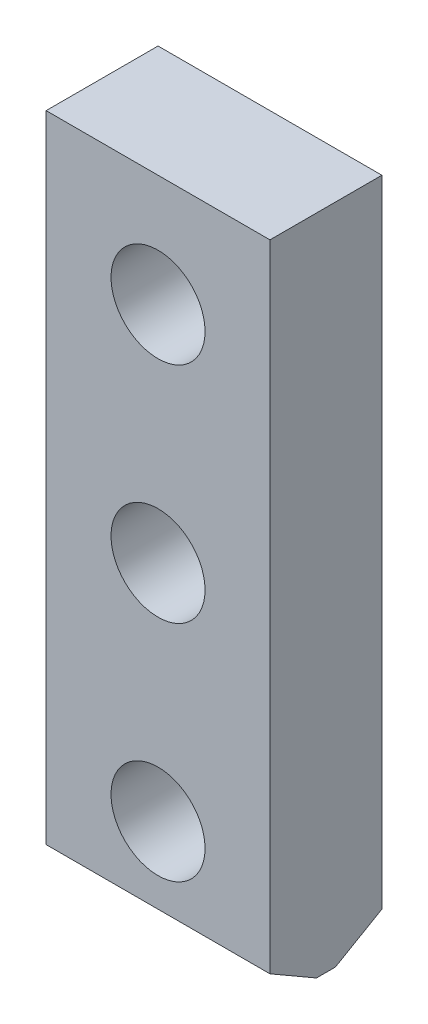
SolidWorks part; units mm, degrees
material "Простая углеродистая сталь"
ref_plane "Спереди" through (0, 0, 0) normal (0, 0, 1) x (1, 0, 0)
ref_plane "Сверху" through (0, 0, 0) normal (0, 1, 0) x (1, 0, 0)
ref_plane "Справа" through (0, 0, 0) normal (1, 0, 0) x (0, 0, -1)
sketch "Эскиз1" plane through (0, 0, 0) normal (0, 0, 1) x (1, 0, 0)
  line L1 (0, 0) -> (50, 0)
  line L2 (0, 0) -> (0, 148)
  line L3 (0, 148) -> (50, 148)
  line L4 (50, 0) -> (50, 148)
  point P5 (25, 148)
  dimension "D1" = 148
  dimension "D2" = 50
extrude "Бобышка-Вытянуть1" add sketch "Эскиз1" along normal blind 25
sketch "Эскиз2" plane through (0, 0, 25) normal (0, 0, 1) x (1, 0, 0)
  line L0 (0, 0) -> (50, 0) construction
  line L1 (50, 0) -> (50, 148) construction
  circle A0 centre (25, 23) radius 10.5
  circle A1 centre (25, 73) radius 10.5
  circle A2 centre (25, 123) radius 10.5
  dimension "D1" = 3
  dimension "D2" = 23
  dimension "D3" = 25
  dimension "D4" = 21
extrude "Вырез-Вытянуть1" cut sketch "Эскиз2" against normal through all
chamfer "Фаска1" distance 6 angle 60 1 edges at (25, 0, 0) first distance on face at (35.5, 73, 0)
chamfer "Фаска2" distance 6 angle 60 1 edges at (25, 0, 25) first distance on face at (35.5, 73, 25)
